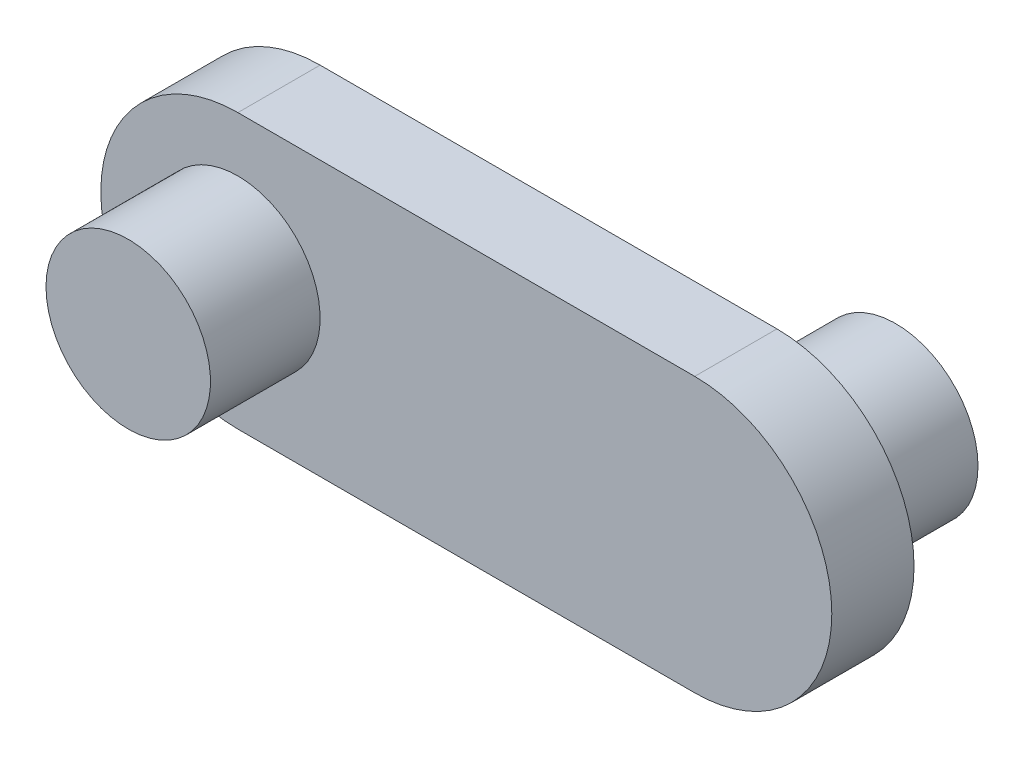
SolidWorks part; units mm, degrees
ref_plane "Alzado" through (0, 0, 0) normal (0, 0, 1) x (1, 0, 0)
ref_plane "Planta" through (0, 0, 0) normal (0, 1, 0) x (1, 0, 0)
ref_plane "Vista lateral" through (0, 0, 0) normal (1, 0, 0) x (0, 0, -1)
sketch "Croquis1" plane through (0, 0, 0) normal (0, 0, 1) x (1, 0, 0)
  line L0 (-8.7925, 13.0309) -> (41.2075, 13.0309)
  line L2 (41.2075, -16.9691) -> (-8.7925, -16.9691)
  line L4 (16.2075, 13.0309) -> (16.2075, -16.9691) construction
  arc A0 (-8.7925, 13.0309) -> (-8.7925, -16.9691) centre (-8.7925, -1.9691) ccw
  arc A1 (41.2075, 13.0309) -> (41.2075, -16.9691) centre (41.2075, -1.9691) cw
  circle A2 centre (-8.7925, -1.9691) radius 10 construction
  circle A3 centre (41.2075, -1.9691) radius 10 construction
  dimension "D1" = 20
  dimension "D2" = 50
extrude "Saliente-Extruir1" add sketch "Croquis1" along normal blind 9
sketch "Croquis2" plane through (0, 0, 9) normal (0, 0, 1) x (1, 0, 0)
  line L0 (16.2075, 13.0309) -> (16.2075, -16.9691) construction
  line L1 (41.2075, 13.0309) -> (-8.7925, 13.0309) construction
  line L2 (-8.7925, -16.9691) -> (41.2075, -16.9691) construction
  circle A0 centre (41.2075, -1.9691) radius 9
  circle A1 centre (-8.7925, -1.9691) radius 9
  dimension "D1" = 18
extrude "Saliente-Extruir2" add sketch "Croquis2" along normal blind 12 contours A1
extrude "Saliente-Extruir3" add sketch "Croquis2<2>" against normal blind 22 contours A0 region at (41.2075, -1.9691, 9)
sketch "Croquis2<2>" plane through (0, 0, 9) normal (0, 0, 1) x (1, 0, 0) same geometry as "Croquis2"
